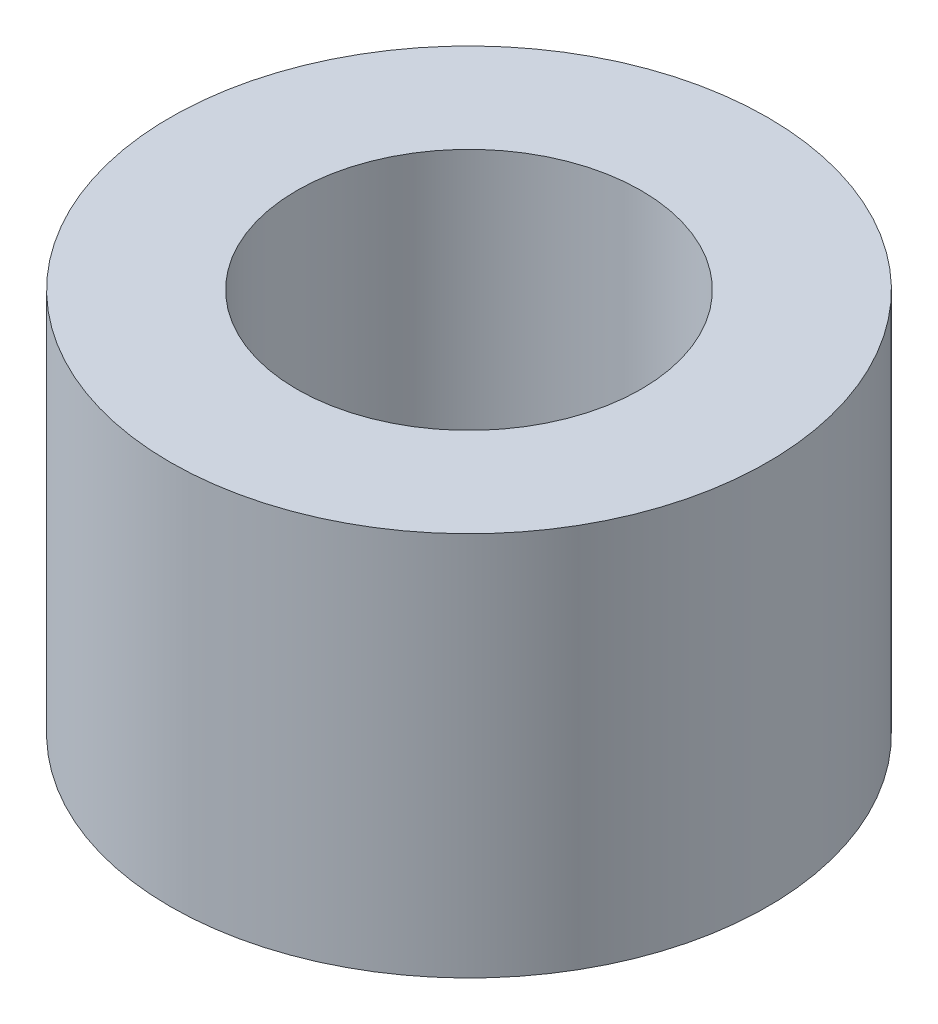
SolidWorks part; units mm, degrees
ref_plane "Front Plane" through (0, 0, 0) normal (0, 0, 1) x (1, 0, 0)
ref_plane "Top Plane" through (0, 0, 0) normal (0, 1, 0) x (1, 0, 0)
ref_plane "Right Plane" through (0, 0, 0) normal (1, 0, 0) x (0, 0, -1)
sketch "Sketch2" plane through (0, 0, 0) normal (0, 1, 0) x (1, 0, 0)
  circle A0 centre (0, 0) radius 1.7
  circle A1 centre (0, 0) radius 2.95
  dimension "D1" = 3.4
  dimension "D2" = 1.25
extrude "Boss-Extrude1" add sketch "Sketch2" along normal blind 3.8
